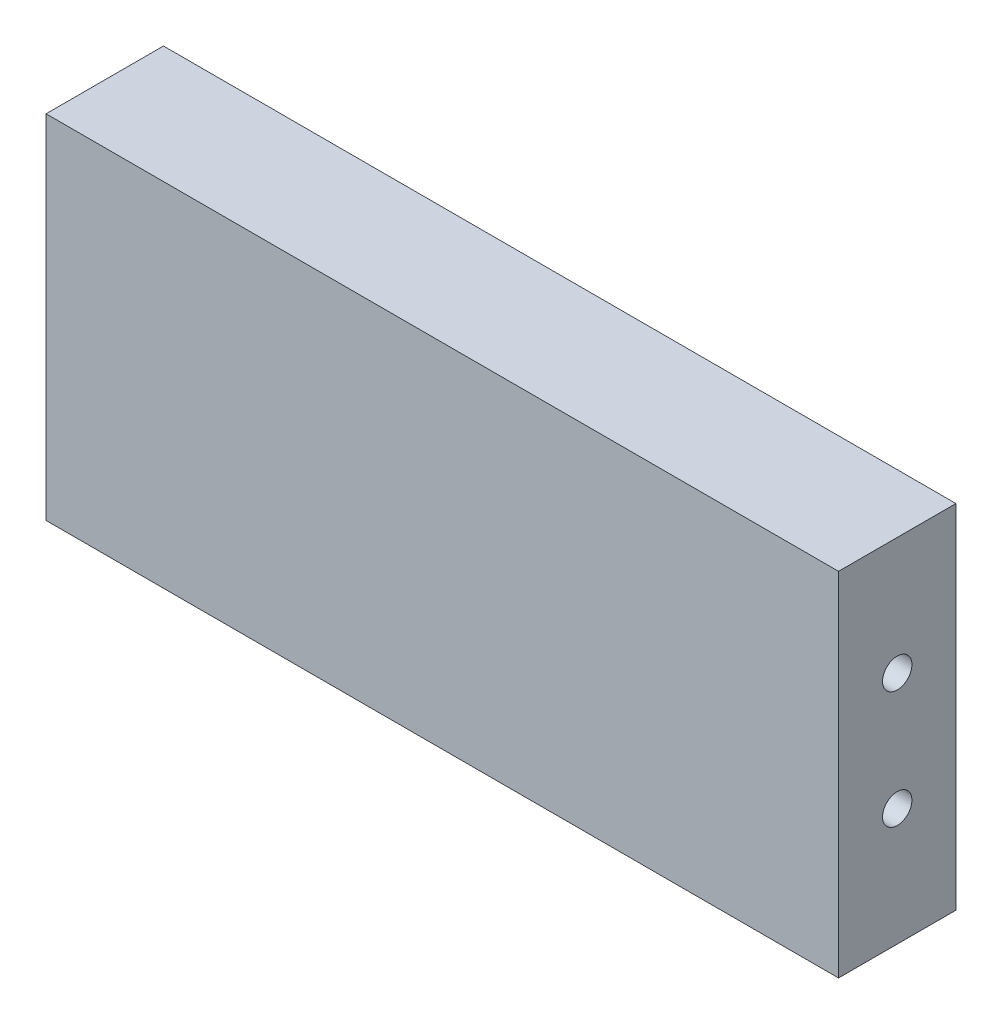
SolidWorks part; units mm, degrees
material "ABS"
ref_plane "Alzado" through (0, 0, 0) normal (0, 0, 1) x (1, 0, 0)
ref_plane "Planta" through (0, 0, 0) normal (0, 1, 0) x (1, 0, 0)
ref_plane "Vista lateral" through (0, 0, 0) normal (1, 0, 0) x (0, 0, -1)
sketch "Sketch1" plane through (0, 0, 0) normal (0, 0, 1) x (1, 0, 0)
  line L1 (-67.5, -30) -> (67.5, -30)
  line L2 (-67.5, -30) -> (-67.5, 30)
  line L3 (-67.5, 30) -> (67.5, 30)
  line L4 (67.5, -30) -> (67.5, 30)
  line L5 (-67.5, -30) -> (67.5, 30) construction
  line L6 (-67.5, 30) -> (67.5, -30) construction
  point P0 (0, 0)
  dimension "D1" = 135
  dimension "D2" = 60
extrude "Boss-Extrude1" add sketch "Sketch1" along normal blind 20
sketch "Sketch2" plane through (0, 0, 0) normal (0, 0, -1) x (-1, 0, 0)
  line L0 (-67.5, 30) -> (67.5, 30) construction
  line L1 (-62.5, -24.9805) -> (62.5, -24.9805)
  line L2 (-62.5, -24.9805) -> (-62.5, 24.9805)
  line L3 (-62.5, 24.9805) -> (62.5, 24.9805)
  line L4 (62.5, -24.9805) -> (62.5, 24.9805)
  line L5 (-62.5, -24.9805) -> (62.5, 24.9805) construction
  line L6 (-62.5, 24.9805) -> (62.5, -24.9805) construction
  line L7 (67.5, 30) -> (67.5, -30) construction
  point P0 (0, 0)
  dimension "D1" = 5.0195
  dimension "D2" = 5
extrude "Cut-Extrude1" cut sketch "Sketch2" against normal blind 15
sketch "Sketch5" plane through (67.5, 0, 0) normal (1, 0, 0) x (0, 0, -1)
  line L0 (0, 0) -> (-20, 0) construction
  line L1 (0, -30) -> (0, 30) construction
  line L2 (-20, -30) -> (-20, 30) construction
  circle A0 centre (-10, 10) radius 2.5
  circle A1 centre (-10, -10) radius 2.5
  point P13 (-10, 0)
  dimension "D1" = 5
  dimension "D2" = 10
  dimension "D3" = 10
extrude "Cut-Extrude3" cut sketch "Sketch5" against normal through all
